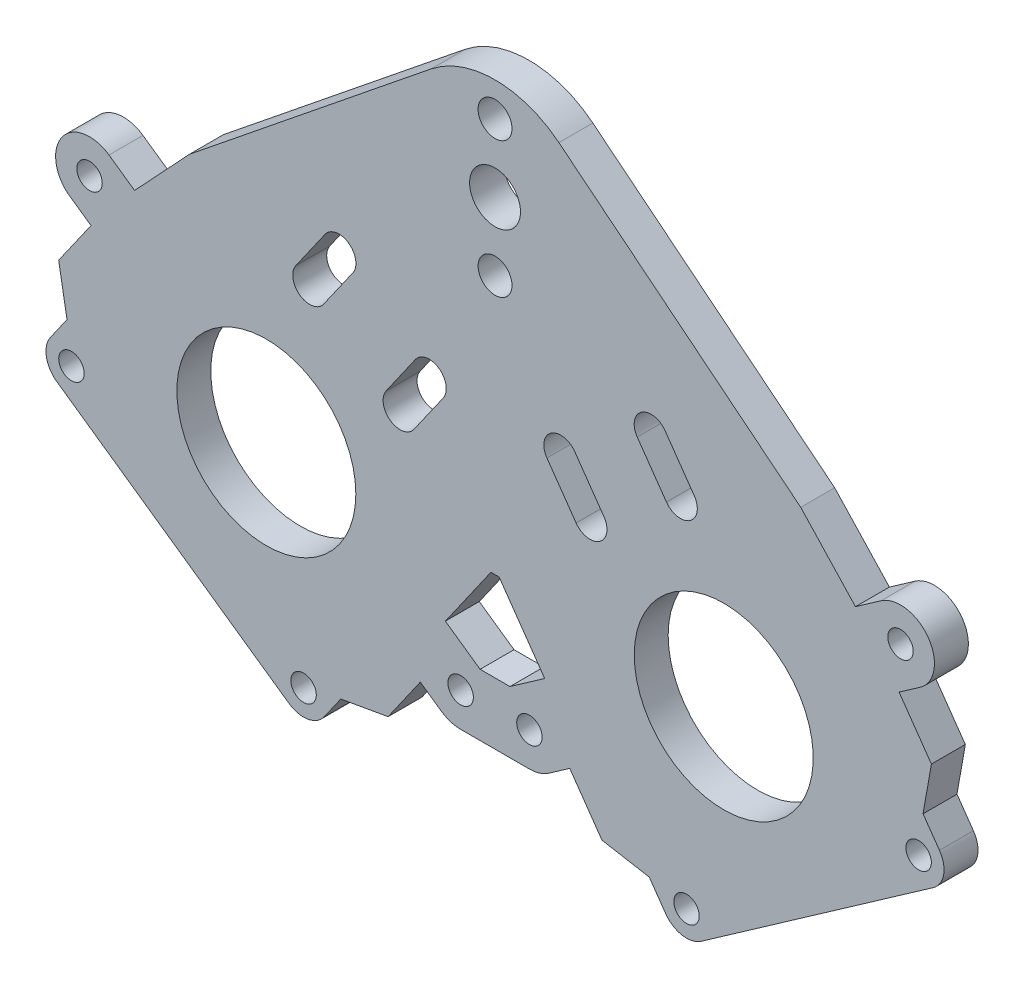
SolidWorks part; units mm, degrees
ref_plane "前视基准面" through (0, 0, 0) normal (0, 0, 1) x (1, 0, 0)
ref_plane "上视基准面" through (0, 0, 0) normal (0, 1, 0) x (1, 0, 0)
ref_plane "右视基准面" through (0, 0, 0) normal (1, 0, 0) x (0, 0, -1)
sketch "草图1" plane through (0, 0, 0) normal (0, 0, 1) x (1, 0, 0)
  line L0 (0, 0) -> (0, 100) construction
  line L1 (0, 100) -> (-26.9581, 61.4999) construction
  line L2 (-36.0325, 86.373) -> (-48.8462, 68.0731)
  line L3 (-0.4813, 61.4798) -> (-13.295, 43.1799)
  line L4 (-34.7415, 87.1955) -> (-29.1288, 88.1851) construction
  line L5 (-27.6344, 87.8538) -> (-1.9622, 69.8779) construction
  line L6 (-49.1775, 66.5787) -> (-47.2056, 55.3951)
  line L7 (-46.3831, 54.1041) -> (-27.2641, 40.7168)
  line L8 (-14.586, 42.3575) -> (-25.7697, 40.3855)
  line L9 (-0.15, 62.9742) -> (-1.1397, 68.5869) construction
  line L10 (0, 100) -> (26.9581, 61.4999) construction
  line L11 (34.7415, 87.1955) -> (29.1288, 88.1851) construction
  line L12 (36.0325, 86.373) -> (48.8462, 68.0731)
  line L13 (49.1775, 66.5787) -> (47.2056, 55.3951)
  line L14 (46.3831, 54.1041) -> (27.2641, 40.7168)
  line L15 (14.586, 42.3575) -> (25.7697, 40.3855)
  line L16 (0.4813, 61.4798) -> (13.295, 43.1799)
  line L17 (0.15, 62.9742) -> (1.1397, 68.5869) construction
  line L18 (27.6344, 87.8538) -> (1.9622, 69.8779) construction
  line L19 (-36.0325, 86.373) -> (-7.5299, 109.3434)
  line L20 (36.0325, 86.373) -> (7.5299, 109.3434)
  line L21 (0.4813, 61.4798) -> (-0.4813, 61.4798)
  line L22 (-21.8435, 80.1367) -> (-18.402, 85.0516) construction
  line L27 (-23.4818, 81.2838) -> (-20.0403, 86.1987)
  line L30 (-20.2052, 78.9895) -> (-16.7637, 83.9044)
  line L31 (-11.1945, 72.6802) -> (-7.7531, 77.5951) construction
  line L32 (-9.5562, 71.533) -> (-6.1148, 76.4479)
  line L33 (-12.8328, 73.8273) -> (-9.3914, 78.7422)
  line L34 (11.1945, 72.6802) -> (7.7531, 77.5951) construction
  line L35 (9.5562, 71.533) -> (6.1148, 76.4479)
  line L36 (12.8328, 73.8273) -> (9.3914, 78.7422)
  line L37 (21.8435, 80.1367) -> (18.402, 85.0516) construction
  line L38 (23.4818, 81.2838) -> (20.0403, 86.1987)
  line L39 (20.2052, 78.9895) -> (16.7637, 83.9044)
  circle A0 centre (0, 100) radius 3
  circle A1 centre (-26.9581, 61.4999) radius 10.55
  arc A2 (-1.1397, 68.5869) -> (-1.9622, 69.8779) centre (-3.1093, 68.2396) ccw construction
  arc A3 (-0.4813, 61.4798) -> (-0.15, 62.9742) centre (-2.1196, 62.6269) ccw construction
  arc A4 (-13.295, 43.1799) -> (-14.586, 42.3575) centre (-14.9333, 44.3271) cw
  arc A5 (-25.7697, 40.3855) -> (-27.2641, 40.7168) centre (-26.1169, 42.3551) cw
  arc A6 (-47.2056, 55.3951) -> (-46.3831, 54.1041) centre (-45.236, 55.7424) ccw
  arc A7 (-48.8462, 68.0731) -> (-49.1775, 66.5787) centre (-47.2079, 66.926) ccw
  arc A8 (-36.0325, 86.373) -> (-34.7415, 87.1955) centre (-34.3942, 85.2258) cw construction
  arc A9 (-29.1288, 88.1851) -> (-27.6344, 87.8538) centre (-28.7815, 86.2155) cw construction
  circle A10 centre (26.9581, 61.4999) radius 10.55
  arc A11 (36.0325, 86.373) -> (34.7415, 87.1955) centre (34.3942, 85.2258) ccw construction
  arc A12 (48.8462, 68.0731) -> (49.1775, 66.5787) centre (47.2079, 66.926) cw
  arc A13 (47.2056, 55.3951) -> (46.3831, 54.1041) centre (45.236, 55.7424) cw
  arc A14 (25.7697, 40.3855) -> (27.2641, 40.7168) centre (26.1169, 42.3551) ccw
  arc A15 (13.295, 43.1799) -> (14.586, 42.3575) centre (14.9333, 44.3271) ccw
  arc A16 (0.4813, 61.4798) -> (0.15, 62.9742) centre (2.1196, 62.6269) cw construction
  arc A17 (1.1397, 68.5869) -> (1.9622, 69.8779) centre (3.1093, 68.2396) cw construction
  arc A18 (29.1288, 88.1851) -> (27.6344, 87.8538) centre (28.7815, 86.2155) ccw construction
  arc A19 (7.5299, 109.3434) -> (-7.5299, 109.3434) centre (0, 100) ccw
  circle A20 centre (0, 100) radius 8 construction
  circle A21 centre (0, 108) radius 2
  circle A22 centre (0, 92) radius 2
  arc A29 (-23.4818, 81.2838) -> (-20.2052, 78.9895) centre (-21.8435, 80.1367) ccw
  arc A30 (-16.7637, 83.9044) -> (-20.0403, 86.1987) centre (-18.402, 85.0516) ccw
  arc A31 (-9.5562, 71.533) -> (-12.8328, 73.8273) centre (-11.1945, 72.6802) cw
  arc A32 (-9.3914, 78.7422) -> (-6.1148, 76.4479) centre (-7.7531, 77.5951) cw
  arc A33 (9.5562, 71.533) -> (12.8328, 73.8273) centre (11.1945, 72.6802) ccw
  arc A34 (9.3914, 78.7422) -> (6.1148, 76.4479) centre (7.7531, 77.5951) ccw
  arc A35 (23.4818, 81.2838) -> (20.2052, 78.9895) centre (21.8435, 80.1367) cw
  arc A36 (16.7637, 83.9044) -> (20.0403, 86.1987) centre (18.402, 85.0516) cw
  point P16 (-1.2836, 69.4028)
  point P20 (-0.0062, 62.1584)
  point P23 (-13.7702, 42.5013)
  point P26 (-26.5855, 40.2416)
  point P29 (-47.0617, 54.5792)
  point P32 (-49.3214, 67.3945)
  point P35 (-35.5574, 87.0516)
  point P38 (-28.313, 88.329)
  point P73 (-20.1228, 82.5941)
  point P80 (-9.4738, 75.1376)
  point P87 (9.4738, 75.1376)
  point P94 (20.1228, 82.5941)
  dimension "D2" = 6
  dimension "D6" = 21.1
  dimension "D9" = 2
  dimension "D14" = 12
  dimension "D15" = 16
  dimension "D16" = 4
  dimension "D17" = 6.5
  dimension "D18" = 2
  dimension "D1" = 100
  dimension "D3" = 43.4
  dimension "D4" = 38.4
  dimension "D5" = 21.2
  dimension "D7" = 135
  dimension "D8" = 135
  dimension "D10" = 31.34
  dimension "D11" = 23.34
  dimension "D12" = 35
  dimension "D13" = 47
  dimension "D19" = 3
  dimension "D20" = 3
extrude "凸台-拉伸1" add sketch "草图1" along normal blind 4
sketch "草图2" plane through (0, 0, 4) normal (0, 0, 1) x (1, 0, 0)
  line L0 (-36.0325, 86.373) -> (-47.306, 74.2827)
  line L1 (-47.306, 74.2827) -> (-49.7635, 76.0034)
  line L2 (-49.7635, 76.0034) -> (-55.4993, 67.8119)
  line L3 (-55.4993, 67.8119) -> (-48.5352, 62.9356)
  line L4 (-49.1775, 66.5787) -> (-47.2056, 55.3951) construction
  line L5 (-36.0325, 86.373) -> (-48.8462, 68.0731) construction
  line L6 (-49.1775, 66.5787) -> (-48.5352, 62.9356)
  line L7 (-36.0325, 86.373) -> (-48.8462, 68.0731)
  line L8 (0, 100) -> (0, 112) construction
  line L9 (36.0325, 86.373) -> (48.8462, 68.0731)
  line L10 (49.1775, 66.5787) -> (48.5352, 62.9356)
  line L11 (55.4993, 67.8119) -> (48.5352, 62.9356)
  line L12 (49.7635, 76.0034) -> (55.4993, 67.8119)
  line L13 (47.306, 74.2827) -> (49.7635, 76.0034)
  line L14 (36.0325, 86.373) -> (47.306, 74.2827)
  line L15 (-46.3831, 54.1041) -> (-27.2641, 40.7168) construction
  line L16 (-18.2291, 41.7151) -> (-13.1491, 38.158)
  line L17 (-25.7697, 40.3855) -> (-14.586, 42.3575) construction
  line L18 (-13.1491, 38.158) -> (-7.4133, 46.3495)
  line L19 (-7.4133, 46.3495) -> (-9.8708, 48.0703)
  line L20 (-13.295, 43.1799) -> (-0.4813, 61.4798) construction
  line L21 (-18.2291, 41.7151) -> (-14.586, 42.3575)
  line L22 (-13.295, 43.1799) -> (-9.8708, 48.0703)
  line L23 (13.295, 43.1799) -> (9.8708, 48.0703)
  line L24 (18.2291, 41.7151) -> (14.586, 42.3575)
  line L25 (7.4133, 46.3495) -> (9.8708, 48.0703)
  line L26 (13.1491, 38.158) -> (7.4133, 46.3495)
  line L27 (18.2291, 41.7151) -> (13.1491, 38.158)
  arc A0 (-48.8462, 68.0731) -> (-49.1775, 66.5787) centre (-47.2079, 66.926) ccw construction
  arc A1 (-48.8462, 68.0731) -> (-49.1775, 66.5787) centre (-47.2079, 66.926) ccw
  arc A2 (7.5299, 109.3434) -> (-7.5299, 109.3434) centre (0, 100) ccw construction
  arc A3 (48.8462, 68.0731) -> (49.1775, 66.5787) centre (47.2079, 66.926) cw
  arc A4 (-14.586, 42.3575) -> (-13.295, 43.1799) centre (-14.9333, 44.3271) ccw construction
  arc A5 (-14.586, 42.3575) -> (-13.295, 43.1799) centre (-14.9333, 44.3271) ccw
  arc A6 (14.586, 42.3575) -> (13.295, 43.1799) centre (14.9333, 44.3271) cw
  dimension "D1" = 2.3
  dimension "D2" = 3
  dimension "D3" = 10
  dimension "D4" = 6
  dimension "D5" = 3
extrude "凸台-拉伸2" add sketch "草图2" against normal up to surface (4 mm away) up to face at (2, 108, 0)
sketch "草图3" plane through (0, 0, 4) normal (0, 0, 1) x (1, 0, 0)
  line L0 (-10.2812, 42.2538) -> (-52.6314, 71.9077) construction
  line L1 (-13.1491, 38.158) -> (-7.4133, 46.3495) construction
  line L2 (-49.7635, 76.0034) -> (-55.4993, 67.8119) construction
  line L3 (-31.4563, 57.0807) -> (-39.4864, 45.6126) construction
  line L5 (-46.3831, 54.1041) -> (-27.2641, 40.7168) construction
  line L8 (-25.7697, 40.3855) -> (-18.2291, 41.7151) construction
  line L9 (-48.5352, 62.9356) -> (-47.2056, 55.3951) construction
  line L10 (-25.7697, 40.3855) -> (-18.2291, 41.7151)
  line L11 (-46.3831, 54.1041) -> (-27.2641, 40.7168)
  line L12 (-48.5352, 62.9356) -> (-47.2056, 55.3951)
  line L13 (-55.4993, 67.8119) -> (-48.5352, 62.9356) construction
  line L14 (-53.0418, 66.0912) -> (-48.5352, 62.9356)
  line L15 (-18.2291, 41.7151) -> (-13.1491, 38.158) construction
  line L16 (-18.2291, 41.7151) -> (-15.6065, 39.8787)
  line L17 (-53.0418, 66.0912) -> (-47.306, 74.2827) construction
  line L18 (-9.8708, 48.0703) -> (-15.6065, 39.8787) construction
  line L19 (-53.0418, 66.0912) -> (-58.204, 58.7188)
  line L20 (-58.204, 58.7188) -> (-20.7687, 32.5064)
  line L21 (-20.7687, 32.5064) -> (-15.6065, 39.8787)
  line L23 (0, 100) -> (0, 108) construction
  line L24 (9.8708, 48.0703) -> (15.6065, 39.8787) construction
  line L25 (53.0418, 66.0912) -> (47.306, 74.2827) construction
  line L26 (31.4563, 57.0807) -> (39.4864, 45.6126) construction
  line L27 (10.2812, 42.2538) -> (52.6314, 71.9077) construction
  line L29 (20.7687, 32.5064) -> (15.6065, 39.8787)
  line L30 (58.204, 58.7188) -> (20.7687, 32.5064)
  line L31 (53.0418, 66.0912) -> (58.204, 58.7188)
  line L32 (18.2291, 41.7151) -> (15.6065, 39.8787)
  line L33 (53.0418, 66.0912) -> (48.5352, 62.9356)
  line L34 (48.5352, 62.9356) -> (47.2056, 55.3951)
  line L35 (46.3831, 54.1041) -> (27.2641, 40.7168)
  line L36 (25.7697, 40.3855) -> (18.2291, 41.7151)
  arc A0 (-27.2641, 40.7168) -> (-25.7697, 40.3855) centre (-26.1169, 42.3551) ccw construction
  arc A1 (-47.2056, 55.3951) -> (-46.3831, 54.1041) centre (-45.236, 55.7424) ccw construction
  arc A2 (-27.2641, 40.7168) -> (-25.7697, 40.3855) centre (-26.1169, 42.3551) ccw
  arc A3 (-47.2056, 55.3951) -> (-46.3831, 54.1041) centre (-45.236, 55.7424) ccw
  arc A4 (47.2056, 55.3951) -> (46.3831, 54.1041) centre (45.236, 55.7424) cw
  arc A5 (27.2641, 40.7168) -> (25.7697, 40.3855) centre (26.1169, 42.3551) cw
  dimension "D1" = 3
extrude "凸台-拉伸3" add sketch "草图3" against normal up to surface (4 mm away) up to face at (0, 60.2815, 0)
sketch "草图4" plane through (0, 0, 4) normal (0, 0, 1) x (1, 0, 0)
  line L0 (22.5702, 38.6509) -> (49.9299, 57.8083) construction
  line L1 (26.9581, 61.4999) -> (36.25, 48.2296) construction
  line L2 (20.7687, 32.5064) -> (58.204, 58.7188) construction
  line L3 (0, 100) -> (0, 92) construction
  line L4 (-26.9581, 61.4999) -> (-36.25, 48.2296) construction
  line L5 (-22.5702, 38.6509) -> (-49.9299, 57.8083) construction
  circle A0 centre (49.9299, 57.8083) radius 1.5
  circle A1 centre (22.5702, 38.6509) radius 1.5
  circle A2 centre (-22.5702, 38.6509) radius 1.5
  circle A3 centre (-49.9299, 57.8083) radius 1.5
  dimension "D1" = 3
  dimension "D2" = 33.4
  dimension "D3" = 16.2
extrude "切除-拉伸1" cut sketch "草图4" against normal through all
sketch "草图5" plane through (0, 0, 4) normal (0, 0, 1) x (1, 0, 0)
  line L0 (26.9581, 61.4999) -> (38.5443, 44.953) construction
  line L1 (-12.2458, 53.3956) -> (-4.0543, 47.6598) construction
  line L2 (20.7687, 32.5064) -> (58.204, 58.7188) construction
  line L3 (1.76, 50.9364) -> (5.8557, 53.8043)
  line L4 (0.4813, 61.4798) -> (9.8708, 48.0703) construction
  line L5 (6.3486, 44.3832) -> (7.9869, 45.5304)
  line L6 (22.5702, 38.6509) -> (12.2458, 53.3956) construction
  line L7 (12.2458, 53.3956) -> (4.0543, 47.6598) construction
  line L8 (7.4133, 46.3495) -> (13.1491, 38.158) construction
  line L9 (7.9869, 45.5304) -> (7.4133, 46.3495)
  line L10 (7.4133, 46.3495) -> (9.8708, 48.0703)
  line L11 (9.8708, 48.0703) -> (5.8557, 53.8043)
  line L12 (55.4993, 67.8119) -> (49.7635, 76.0034) construction
  line L13 (45.5027, 81.5654) -> (42.4854, 79.4527)
  line L14 (47.306, 74.2827) -> (36.0325, 86.373) construction
  line L15 (42.4854, 79.4527) -> (47.306, 74.2827)
  line L16 (47.306, 74.2827) -> (49.7635, 76.0034)
  line L17 (49.7635, 76.0034) -> (50.3306, 75.1935)
  line L18 (0, 100) -> (0, 92) construction
  line L19 (-22.5702, 38.6509) -> (-12.2458, 53.3956) construction
  line L20 (-26.9581, 61.4999) -> (-38.5443, 44.953) construction
  line L21 (-49.7635, 76.0034) -> (-50.3306, 75.1935)
  line L22 (-47.306, 74.2827) -> (-49.7635, 76.0034)
  line L23 (-42.4854, 79.4527) -> (-47.306, 74.2827)
  line L24 (-45.5027, 81.5654) -> (-42.4854, 79.4527)
  line L25 (-9.8708, 48.0703) -> (-5.8557, 53.8043)
  line L26 (-7.4133, 46.3495) -> (-9.8708, 48.0703)
  line L27 (-7.9869, 45.5304) -> (-7.4133, 46.3495)
  line L28 (-6.3486, 44.3832) -> (-7.9869, 45.5304)
  line L29 (-1.76, 50.9364) -> (-5.8557, 53.8043)
  circle A0 centre (4.0543, 47.6598) radius 1.5
  circle A1 centre (47.797, 78.2888) radius 1.5
  arc A2 (1.76, 50.9364) -> (6.3486, 44.3832) centre (4.0543, 47.6598) ccw
  arc A3 (45.5027, 81.5654) -> (50.3306, 75.1935) centre (47.797, 78.2888) cw
  arc A4 (-45.5027, 81.5654) -> (-50.3306, 75.1935) centre (-47.797, 78.2888) ccw
  arc A5 (-1.76, 50.9364) -> (-6.3486, 44.3832) centre (-4.0543, 47.6598) cw
  circle A6 centre (-47.797, 78.2888) radius 1.5
  circle A7 centre (-4.0543, 47.6598) radius 1.5
  dimension "D1" = 53.4
  dimension "D2" = 3
  dimension "D3" = 4
  dimension "D4" = 18
extrude "凸台-拉伸4" add sketch "草图5" against normal up to surface (4 mm away) up to face at (51.4299, 57.8083, 0)
sketch "草图6" plane through (0, 0, 0) normal (0, 0, -1) x (-1, 0, 0)
  line L0 (-47.6274, 73.3007) -> (-51.4358, 67.8618)
  line L1 (-51.4358, 67.8618) -> (-50.4535, 62.2909)
  line L2 (-50.4535, 62.2909) -> (-52.3873, 59.529)
  line L3 (-51.6506, 55.3509) -> (-24.2909, 36.1934)
  line L4 (-18.1789, 39.692) -> (-20.1127, 36.9301) construction
  line L5 (-20.1127, 36.9301) -> (-18.1789, 39.692)
  line L6 (-18.1789, 39.692) -> (-12.608, 40.6743)
  line L7 (-12.608, 40.6743) -> (-8.8061, 46.104)
  line L8 (-7.9869, 45.5304) -> (-13.1491, 38.158)
  line L9 (-47.6274, 73.3007) -> (-50.3306, 75.1935)
  line L11 (-8.8061, 46.104) -> (-7.9869, 45.5304)
  line L12 (-13.1491, 38.158) -> (-15.6065, 39.8787)
  line L13 (-15.6065, 39.8787) -> (-20.7687, 32.5064)
  line L14 (-20.7687, 32.5064) -> (-58.204, 58.7188)
  line L15 (-58.204, 58.7188) -> (-53.0418, 66.0912)
  line L16 (-53.0418, 66.0912) -> (-55.4993, 67.8119)
  line L17 (-55.4993, 67.8119) -> (-50.3306, 75.1935)
  line L18 (0, 100) -> (0, 92) construction
  line L19 (55.4993, 67.8119) -> (50.3306, 75.1935)
  line L20 (53.0418, 66.0912) -> (55.4993, 67.8119)
  line L21 (58.204, 58.7188) -> (53.0418, 66.0912)
  line L22 (20.7687, 32.5064) -> (58.204, 58.7188)
  line L23 (15.6065, 39.8787) -> (20.7687, 32.5064)
  line L24 (13.1491, 38.158) -> (15.6065, 39.8787)
  line L25 (8.8061, 46.104) -> (7.9869, 45.5304)
  line L26 (47.6274, 73.3007) -> (50.3306, 75.1935)
  line L27 (7.9869, 45.5304) -> (13.1491, 38.158)
  line L28 (12.608, 40.6743) -> (8.8061, 46.104)
  line L29 (18.1789, 39.692) -> (12.608, 40.6743)
  line L30 (20.1127, 36.9301) -> (18.1789, 39.692)
  line L31 (51.6506, 55.3509) -> (24.2909, 36.1934)
  line L32 (50.4535, 62.2909) -> (52.3873, 59.529)
  line L33 (51.4358, 67.8618) -> (50.4535, 62.2909)
  line L34 (47.6274, 73.3007) -> (51.4358, 67.8618)
  arc A0 (-52.3873, 59.529) -> (-51.6506, 55.3509) centre (-49.9299, 57.8083) ccw
  arc A1 (-52.3873, 59.529) -> (-51.6506, 55.3509) centre (-49.9299, 57.8083) ccw construction
  arc A2 (-24.2909, 36.1934) -> (-20.1127, 36.9301) centre (-22.5702, 38.6509) ccw
  arc A3 (24.2909, 36.1934) -> (20.1127, 36.9301) centre (22.5702, 38.6509) cw
  arc A4 (52.3873, 59.529) -> (51.6506, 55.3509) centre (49.9299, 57.8083) cw
extrude "切除-拉伸2" cut sketch "草图6" against normal through all
sketch "草图7" plane through (0, 0, 4) normal (0, 0, 1) x (1, 0, 0)
  line L0 (-4.0543, 43.6598) -> (4.0543, 43.6598)
  line L1 (-1.76, 50.9364) -> (1.76, 50.9364)
  arc A0 (-6.3486, 44.3832) -> (-1.76, 50.9364) centre (-4.0543, 47.6598) ccw construction
  arc A1 (1.76, 50.9364) -> (6.3486, 44.3832) centre (4.0543, 47.6598) ccw construction
  arc A2 (1.76, 50.9364) -> (4.0543, 43.6598) centre (4.0543, 47.6598) ccw
  arc A3 (-4.0543, 43.6598) -> (-1.76, 50.9364) centre (-4.0543, 47.6598) ccw
extrude "凸台-拉伸5" add sketch "草图7" against normal up to surface (4 mm away) up to face at (0, 61.0947, 0)
